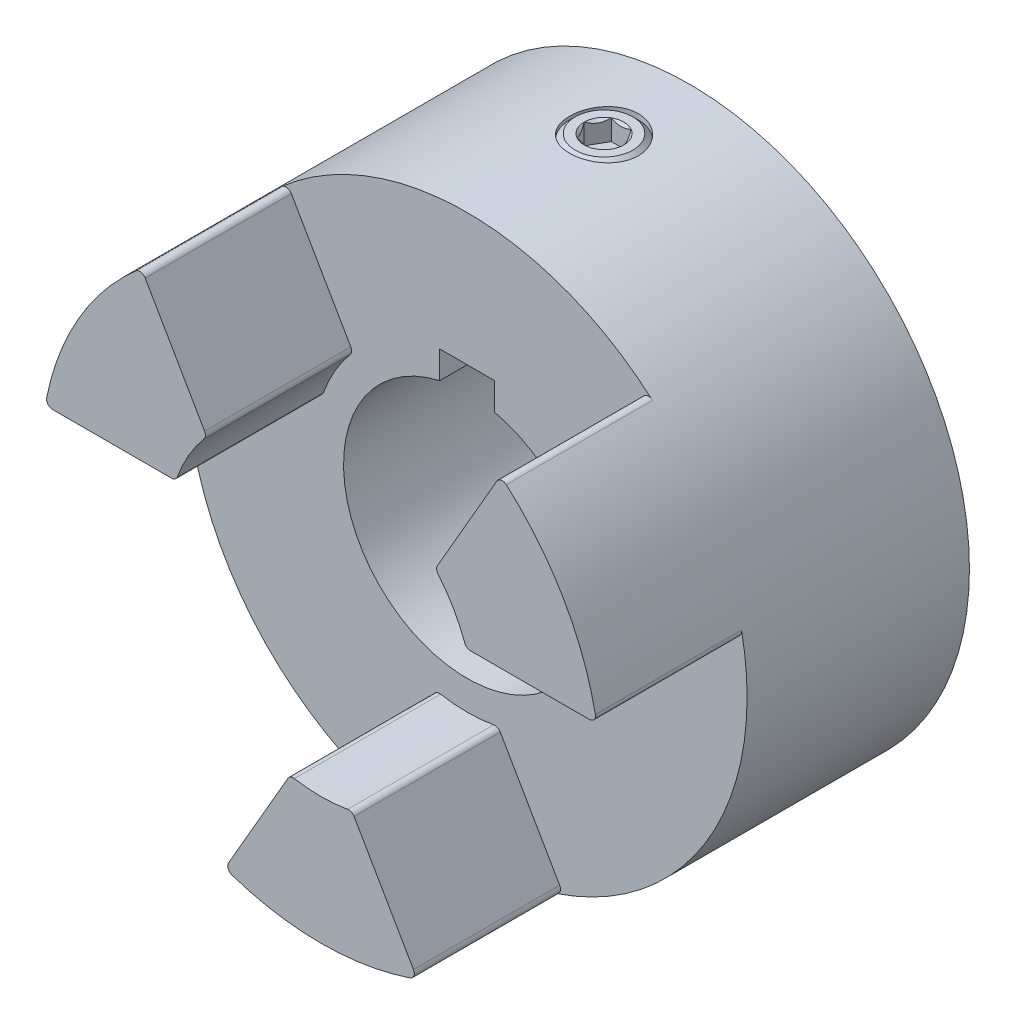
SolidWorks part; units mm, degrees
ref_plane "Front" through (0, 0, 0) normal (0, 0, 1) x (1, 0, 0)
ref_plane "Top" through (0, 0, 0) normal (0, 1, 0) x (1, 0, 0)
ref_plane "Right" through (0, 0, 0) normal (1, 0, 0) x (0, 0, -1)
sketch "Sketch3" plane through (0, 0, 0) normal (1, 0, 0) x (0, 0, -1)
  line L0 (36.1156, 0) -> (-36.1156, 0) construction
  circle A0 centre (0, 0) radius 7.7629 construction
  circle A1 centre (0, 0) radius 14.2875 construction
  circle A2 centre (0, 0) radius 32.3453 construction
  point P7 (0, 7.7629)
  point P8 (0, -7.7629)
  point P9 (0, 14.2875)
  point P10 (0, -14.2875)
  point P11 (0, 32.3453)
  point P12 (0, -32.3453)
  point P13 (9.1281, 0)
  point P14 (-7.7629, 0)
  point P15 (7.7629, 0)
  point P16 (-7.7629, 32.3453)
  point P17 (36.1156, 32.3453)
  point P18 (9.1281, 32.3453)
  dimension "OD" = 64.6906
  dimension "Shaft Dia" = 28.575
  dimension "Overall Lg" = 72.2313
  dimension "Bore Depth" = 26.9875
  dimension "Lug Lg" = 16.891
sketch "Sketch1" plane through (0, 0, 0) normal (0, 0, 1) x (1, 0, 0)
  circle A0 centre (0, 0) radius 32.3453
  circle A1 centre (0, 0) radius 14.2875 construction
extrude "Boss-Extrude1" add sketch "Sketch1" against normal up to vertex (36.1156 mm away) from vertex up to point (0, 0, -36.1156) starting at point (0, 0, -9.1281)
sketch "Sketch10" [suppressed] plane through (0, 0, -3.5719) normal (0, 0, 1) x (1, 0, 0)
  arc A14 (-1.0963, -4.1108) -> (1.0963, -4.1108) centre (0, 0) ccw
  arc A15 (-3.4409, -7.1529) -> (-1.0963, -4.1108) centre (-9.5758, 0) ccw
  arc A19 (1.0963, -4.1108) -> (3.4409, -7.1529) centre (9.5758, 0) ccw
  circle A32 centre (0, 0) radius 7.9375 construction
  arc A33 (-3.4409, -7.1529) -> (3.4409, -7.1529) centre (0, 0) ccw
  point P0 (0, -4.2545)
  point P1 (0, -7.9375)
  dimension "D1" = 3.683
  dimension "D4" = 9.4234
  dimension "D2" = 6.8819
  dimension "D3" = 2.1926
extrude "Boss-Extrude4" [suppressed] add sketch "Sketch10" along normal up to vertex up to point (0, 0, 7.7629)
fillet "Fillet2" [suppressed] radius 0.381
other "Move Face3" [suppressed] parameters "D1"=90
pattern_circular "CirPattern2" [suppressed] count 2 over 360 of bodies 116
sketch "Sketch11" [suppressed] plane through (0, 0, -5.9531) normal (0, 0, 1) x (1, 0, 0)
  arc A0 (-1.5825, -7.8835) -> (1.5738, -7.8835) centre (-0.0044, -0.0397) ccw
  arc A1 (-1.5825, -7.8835) -> (-2.9616, -8.354) centre (-1.8681, -9.3029) ccw
  arc A2 (-2.9616, -8.354) -> (-4.9794, -11.8231) centre (5.1535, -15.3956) ccw
  arc A3 (-4.9794, -11.8231) -> (-4.4308, -12.9555) centre (-4.1442, -12.1175) ccw
  arc A4 (-4.4308, -12.9555) -> (4.4176, -12.96) centre (0, 0) ccw
  arc A5 (4.4176, -12.96) -> (4.9692, -11.8231) centre (4.1308, -12.1185) ccw
  arc A6 (4.9692, -11.8231) -> (2.9523, -8.354) centre (-5.1643, -15.3938) ccw
  arc A7 (2.9523, -8.354) -> (1.5738, -7.8835) centre (1.8592, -9.3021) ccw
  circle A8 centre (0, 0) radius 13.6922 construction
  point P18 (-0.007, -13.6922)
  point P19 (-0.0044, -8.0407)
  dimension "D1" = 1.4478
  dimension "D2" = 8.001
  dimension "D3" = 10.7442
  dimension "D4" = 0.889
  dimension "D9" = 5.6515
  dimension "D5" = 5.072
  dimension "D6" = 3.1563
  dimension "D7" = 5.9139
  dimension "D8" = 9.9486
extrude "Boss-Extrude5" [suppressed] add sketch "Sketch11" along normal up to vertex up to point (0, 0, 7.7629)
other "Move Face1" [suppressed] parameters "D1"=90
pattern_circular "CirPattern3" [suppressed] count 2 over 360 of bodies 118
sketch "Sketch12" [suppressed] plane through (0, 0, -6.1516) normal (0, 0, 1) x (1, 0, 0)
  line L0 (-5.1097, -10.267) -> (-8.533, -13.6894)
  line L1 (8.533, -13.6894) -> (5.1097, -10.267)
  arc A0 (-2.3442, -9.4968) -> (2.3442, -9.4968) centre (0, 0) ccw
  arc A1 (-2.3442, -9.4968) -> (-5.1097, -10.267) centre (-3.0443, -12.333) ccw
  arc A2 (-8.533, -13.6894) -> (-8.3299, -15.1215) centre (-7.8934, -14.3292) ccw
  arc A3 (-8.3299, -15.1215) -> (8.3299, -15.1215) centre (0, 0) ccw
  arc A4 (8.3299, -15.1215) -> (8.533, -13.6894) centre (7.8934, -14.3292) ccw
  arc A5 (5.1097, -10.267) -> (2.3442, -9.4968) centre (3.0443, -12.333) ccw
  circle A6 centre (0, 0) radius 17.2641 construction
  point P16 (0, -9.7819)
  point P17 (0, -17.2641)
  dimension "D1" = 7.4822
  dimension "D2" = 10.2193
  dimension "D3" = 4.6884
  dimension "D4" = 17.066
  dimension "D5" = 16.6598
extrude "Boss-Extrude6" [suppressed] add sketch "Sketch12" along normal up to vertex up to point (0, 0, 7.7629)
other "Move Face2" [suppressed] parameters "D1"=90
pattern_circular "CirPattern4" [suppressed] count 2 over 360 of bodies 120
sketch "Sketch2" plane through (0, 0, -9.1281) normal (0, 0, 1) x (1, 0, 0)
  line L0 (-11.1144, -30.3758) -> (-3.5662, -17.302)
  line L2 (3.5662, -17.302) -> (11.1144, -30.3758)
  circle A0 centre (0, 0) radius 32.3453 construction
  arc A1 (-11.1144, -30.3758) -> (11.1144, -30.3758) centre (0, 0) ccw
  arc A2 (-3.5662, -17.302) -> (3.5662, -17.302) centre (0, 0) ccw
  circle A3 centre (0, 0) radius 5.5626 construction
  dimension "Spider Inner body Dia" = 35.3314
  dimension "Spider Leg Thickness" = 11.1252
  dimension "D4" = 7.1324
  dimension "D1" = 60
extrude "Boss-Extrude2" add sketch "Sketch2" along normal up to vertex (16.891 mm away) up to point (0, 0, 7.7629)
fillet "Fillet1" radius 0.7132 4 edges at (3.5662, -17.302, -0.6826) (-3.5662, -17.302, -0.6826)
pattern_circular "CirPattern1" count 3 over 360 about axis through (0, 0, -36.1156) along (0, 0, 1) of "Boss-Extrude2", "Fillet1"
sketch "Sketch15" plane through (0, 0, 0) normal (0, 0, 1) x (1, 0, 0)
  circle A0 centre (0, 0) radius 14.2875
extrude "Cut-Extrude5" cut sketch "Sketch15" against normal through all and the other way through all
chamfer "Chamfer1" distance 1.2938 angle 56 2 edges at (32.3453, 0, -36.1156) (14.2875, 0, -36.1156) first distance on face at (32.3453, 0, -36.1156) first distance on face at (14.2875, 0, -9.1281)
sketch "Sketch4" plane through (0, 0, 0) normal (0, 0, 1) x (1, 0, 0)
  line L1 (-3.175, 17.1053) -> (3.175, 17.1053)
  line L2 (-3.175, 17.1053) -> (-3.175, 13.9303)
  line L4 (3.175, 17.1053) -> (3.175, 13.9303)
  arc A1 (3.175, 13.9303) -> (-3.175, 13.9303) centre (0, 0) ccw
  circle A2 centre (0, 0) radius 14.2875 construction
  dimension "Keyway Ht" = 3.175
  dimension "Keyway Wd" = 6.35
extrude "Cut-Extrude1" cut sketch "Sketch4" against normal through all and the other way through all
sketch "Sketch5" plane through (0, 0, 0) normal (0, 1, 0) x (1, 0, 0)
  line L1 (0, -46.4939) -> (0, 46.4939) construction
  circle A0 centre (0, 24.9396) radius 3.9688
  dimension "Screw Dia" = 7.9375
  dimension "Screw Offset" = 11.176
extrude "Cut-Extrude2" cut sketch "Sketch5" along normal through all
ref_plane "Plane1" through (0, 32.3453, 0) normal (0, 1, 0) x (-1, 0, 0)
sketch "Sketch6" plane through (0, 32.3453, 0) normal (0, 1, 0) x (-1, 0, 0)
  circle A1 centre (0, -24.9396) radius 3.9688
  circle A2 centre (0, -24.9396) radius 3.9688
  dimension "D1" = 0
extrude "Boss-Extrude3" add sketch "Sketch6" against normal blind 9.525 separate body
sketch "Sketch8" plane through (0, 32.3453, 0) normal (0, 1, 0) x (1, 0, 0)
  line L1 (1.1457, 22.9552) -> (2.2914, 24.9396)
  line L2 (2.2914, 24.9396) -> (1.1457, 26.924)
  line L3 (1.1457, 26.924) -> (-1.1457, 26.924)
  line L4 (-1.1457, 26.924) -> (-2.2914, 24.9396)
  line L5 (-2.2914, 24.9396) -> (-1.1457, 22.9552)
  line L6 (-1.1457, 22.9552) -> (1.1457, 22.9552)
  circle A0 centre (0, 24.9396) radius 1.9844 construction
  dimension "D1" = 3.9688
extrude "Cut-Extrude3" cut sketch "Sketch8" against normal blind 2.3813
sketch "Sketch9" plane through (0, 32.3453, 0) normal (0, 1, 0) x (1, 0, 0)
  circle A0 centre (0, 24.9396) radius 2.2914
extrude "Cut-Extrude4" cut sketch "Sketch9" against normal through all draft 45
chamfer "Chamfer3" distance 0.635 angle 45 1 edges at (0, 32.3453, -20.9709)
chamfer "Chamfer4" distance 1.3494 angle 45 1 edges at (0, 22.8203, -20.9709)
sketch "Sketch16" [suppressed] plane through (0, 0, -61.9125) normal (0, 0, -1) x (-1, 0, 0)
  circle A0 centre (0, 0) radius 50.8
  dimension "D1" = 101.6
extrude "Cut-Extrude6" [suppressed] cut sketch "Sketch16" against normal blind 30.3022 flip side to cut
chamfer "Chamfer5" [suppressed] distance 1.778 angle 56
fillet "Fillet3" [suppressed] radius 1.27
move or copy body "Body-Move/Copy1" [suppressed] bodies to move or copy 115 copy no translate (0, -6.35, 0)
sketch "Sketch17" [suppressed] plane through (0, 0, -67.8656) normal (0, 0, -1) x (-1, 0, 0)
  circle A0 centre (0, 0) radius 53.975
  dimension "D1" = 107.95
extrude "Cut-Extrude7" [suppressed] cut sketch "Sketch17" against normal blind 36.576 flip side to cut
move or copy body "Body-Move/Copy2" [suppressed] bodies to move or copy 115 copy no translate (0, -9.525, 0)
fillet "Fillet4" [suppressed] radius 2.54
fillet "Fillet5" [suppressed] radius 1.27
equation "\"D1@Chamfer1\" = \"OD@Sketch3\" * .02"
equation "\"D1@Fillet1\" = \"D4@Sketch2\" * .1"
equation "\"D1@Sketch8\" = \"Screw Dia@Sketch5\" * .5"
equation "\"D1@Cut-Extrude3\" = \"Screw Dia@Sketch5\" * .3"
equation "\"D1@Chamfer3\" = \"Screw Dia@Sketch5\" * .08"
equation "\"D1@Chamfer4\" = \"Screw Dia@Sketch5\" * .17"
